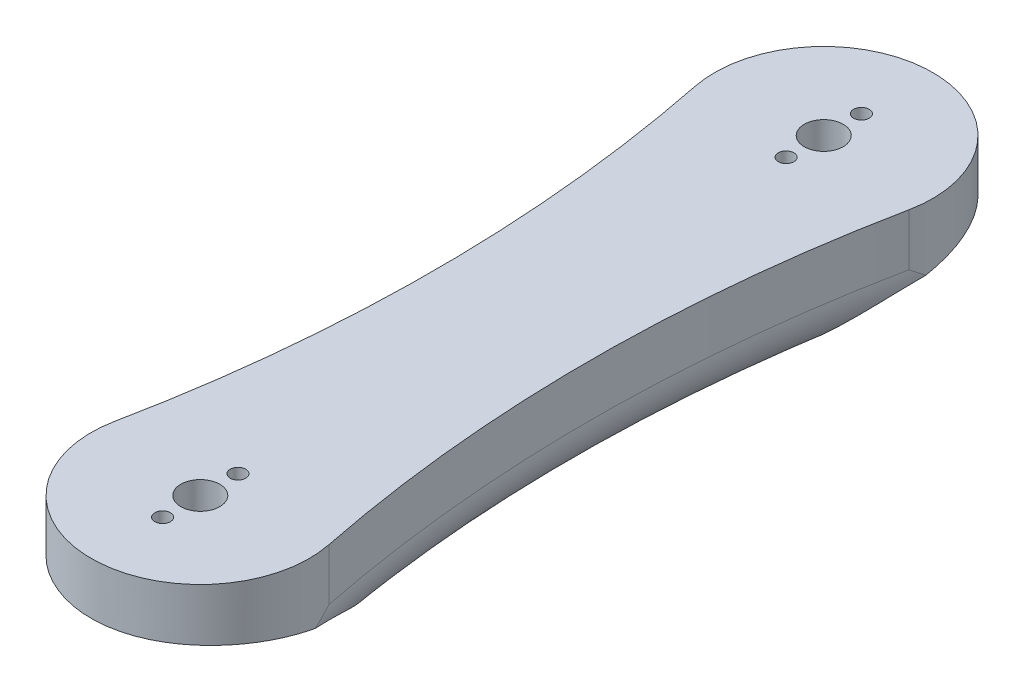
SolidWorks part; units mm, degrees
ref_plane "前视基准面" through (0, 0, 0) normal (0, 0, 1) x (1, 0, 0)
ref_plane "上视基准面" through (0, 0, 0) normal (0, 1, 0) x (1, 0, 0)
ref_plane "右视基准面" through (0, 0, 0) normal (1, 0, 0) x (0, 0, -1)
sketch "草图1" plane through (0, 0, 0) normal (0, 1, 0) x (1, 0, 0)
  line L0 (-32.6031, 6) -> (31.2376, 6) construction
  line L1 (-32.6031, 114) -> (31.2376, 114) construction
  line L2 (0, 120) -> (0, 0) construction
  circle A0 centre (0, 0) radius 21
  circle A1 centre (0, 120) radius 21
  arc A2 (-20.5842, 115.8416) -> (-20.5842, 4.1584) centre (-297, 60) cw
  arc A3 (20.5842, 115.8416) -> (20.5842, 4.1584) centre (297, 60) ccw
  point P9 (-15, 60)
  dimension "D2" = 42
  dimension "D3" = 42
  dimension "D1" = 120
  dimension "D4" = 6
  dimension "D5" = 6
  dimension "D6" = 15
extrude "凸台-拉伸1" add sketch "草图1" along normal blind 16 contours A3 A1 A2 A0 region at (0, 0, -60)
extrude "凸台-拉伸2" add sketch "草图1<3>" along normal blind 21 contours A0 | A1 region at (0, 0, 0) region at (0, 0, -120)
sketch "草图1<3>" plane through (0, 0, 0) normal (0, 1, 0) x (1, 0, 0) same geometry as "草图1"
sketch "草图2" plane through (0, 0, 0) normal (1, 0, 0) x (0, 0, -1)
  line L0 (-21, 0) -> (21, 0)
  line L1 (141, 0) -> (141, 11)
  line L2 (141, 0) -> (141, 21) construction
  line L3 (-21, 0) -> (-21, 11)
  line L4 (-21, 21) -> (-21, 0) construction
  line L6 (115.8416, 16) -> (115.8416, 0) construction
  line L7 (4.1584, 16) -> (4.1584, 0) construction
  line L8 (99, 0) -> (141, 0)
  spline S0 degree 3 poles (-21, 11) (-13.2343, 11.0895) (3.6254, 9.3757) (14.3618, 4.3022) (21, 0) knots 0 0 0 0 0.576072 1 1 1 1
  spline S1 degree 2 poles (141, 11) (118.0276, 12.3317) (99, 0) knots 0 0 0 1 1 1
  dimension "D1" = 11
  dimension "D2" = 11
  dimension "D3" = 42
  dimension "D4" = 42
extrude "切除-拉伸1" cut sketch "草图2" against normal through all both and the other way through all
ref_plane "基准面4" through (0, 15, 0) normal (0, 1, 0) x (1, 0, 0)
fillet "圆角1" radius 11 2 edges at (15, 0, -60) (-15, 0, -60)
sketch "草图3" plane through (0, 15, 0) normal (0, 1, 0) x (1, 0, 0)
  arc A4 (20.5842, 115.8416) -> (20.5842, 4.1584) centre (297, 60) ccw
  arc A5 (-20.5842, 115.8416) -> (20.5842, 115.8416) centre (0, 120) ccw
  arc A6 (-20.5842, 4.1584) -> (-20.5842, 115.8416) centre (-297, 60) ccw
  arc A7 (20.5842, 4.1584) -> (-20.5842, 4.1584) centre (0, 0) ccw
  arc A8 (20.5842, 115.8416) -> (20.5842, 4.1584) centre (297, 60) ccw
  arc A9 (-20.5842, 115.8416) -> (20.5842, 115.8416) centre (0, 120) ccw
  arc A10 (-20.5842, 4.1584) -> (-20.5842, 115.8416) centre (-297, 60) ccw
  arc A11 (20.5842, 4.1584) -> (-20.5842, 4.1584) centre (0, 0) ccw
  dimension "D1" = 0
extrude "凸台-拉伸3" add sketch "草图3" along normal up to surface (6 mm away) up to face at (0, 21, -99)
sketch "草图4" plane through (0, 0, 0) normal (0, 0, 1) x (1, 0, 0)
  circle A0 centre (0, 9) radius 5.75
  dimension "D1" = 11.5
  dimension "D2" = 9
extrude "切除-拉伸2" cut sketch "草图4" against normal blind 124
ref_plane "基准面5" through (20.5842, 21, -115.8416) normal (0.198, 0, -0.9802) x (-0.9802, 0, -0.198)
sketch "草图6" plane through (0, 15, 0) normal (0, 1, 0) x (1, 0, 0)
  circle A0 centre (0, 120) radius 18
  circle A1 centre (0, 0) radius 18
  arc A2 (20.5842, 115.8416) -> (-20.5842, 115.8416) centre (0, 120) ccw construction
  arc A3 (-20.5842, 4.1584) -> (20.5842, 4.1584) centre (0, 0) ccw construction
  dimension "D1" = 3
  dimension "D2" = 3
extrude "切除-拉伸4" cut sketch "草图6" against normal blind 21
sketch "草图7" plane through (0, 15, 0) normal (0, -1, 0) x (1, 0, 0)
  line L0 (7.3871, -118.5076) -> (33.7812, -113.1755) construction
  line L1 (0, 0) -> (0, -120) construction
  line L2 (0, -60) -> (53.7066, -60) construction
  circle A0 centre (0, -120) radius 3.75
  circle A1 centre (0, -112.75) radius 1.5
  circle A2 centre (0, -127.25) radius 1.5
  circle A3 centre (0, -120) radius 18 construction
  circle A4 centre (0, 7.25) radius 1.5
  circle A5 centre (0, -7.25) radius 1.5
  circle A6 centre (0, 0) radius 3.75
  dimension "D1" = 7.5
  dimension "D2" = 3
  dimension "D3" = 3
  dimension "D4" = 7.25
  dimension "D5" = 7.25
extrude "切除-拉伸5" cut sketch "草图7" against normal through all
